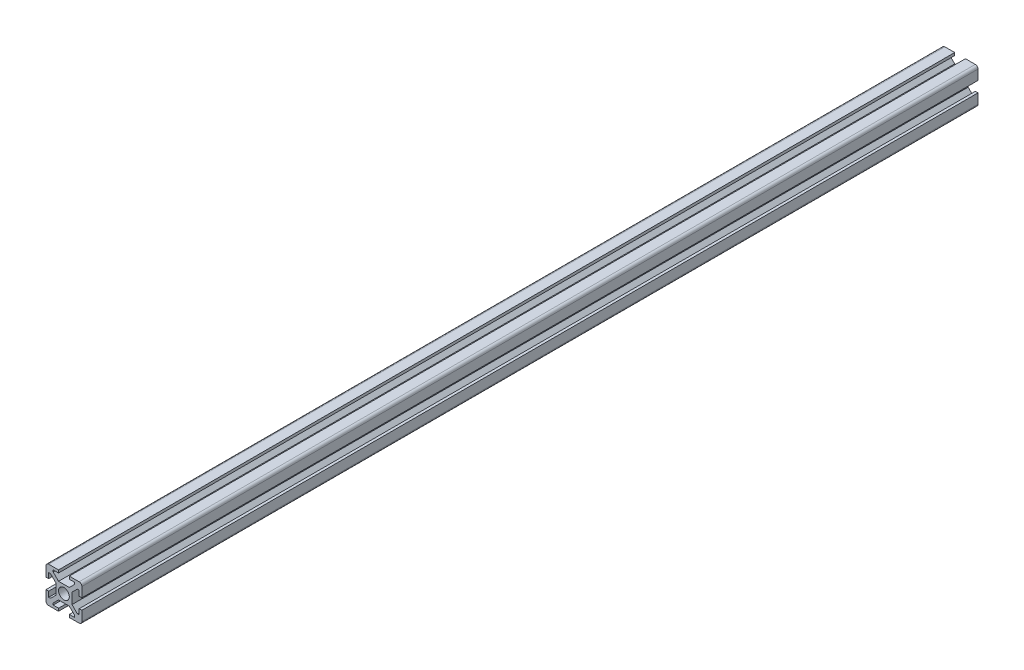
SolidWorks part; units mm, degrees
ref_plane "Plan de face" through (0, 0, 0) normal (0, 0, 1) x (1, 0, 0)
ref_plane "Plan de dessus" through (0, 0, 0) normal (0, 1, 0) x (1, 0, 0)
ref_plane "Plan de droite" through (0, 0, 0) normal (1, 0, 0) x (0, 0, -1)
sketch "Esquisse1" plane through (0, 0, 0) normal (0, 0, 1) x (1, 0, 0)
  line L0 (-10, 10) -> (10, -10) construction
  line L1 (-10, 10) -> (10, 10)
  line L2 (-10, 10) -> (-10, -10)
  line L3 (-10, -10) -> (10, -10)
  line L4 (10, 10) -> (10, -10)
  dimension "D1" = 20
extrude "Extrusion1" add sketch "Esquisse1" along normal mid plane 500
fillet "Congé1" radius 1.5 4 edges at (-10, -10, 0) (10, -10, 0) (-10, 10, 0) (10, 10, 0)
sketch "Esquisse2" plane through (0, 0, -250) normal (0, 0, -1) x (-1, 0, 0)
  line L0 (-10, 3) -> (-10, -3)
  line L1 (-10, -8.5) -> (-10, 8.5) construction
  line L2 (-10, -3) -> (-8.5, -3)
  line L3 (-8.5, -3) -> (-8.5, -6)
  line L4 (-8.5, 6) -> (-7.5, 6)
  line L5 (-4.5, -3) -> (-4.5, 3)
  line L6 (-7.5, 6) -> (-4.5, 3)
  line L7 (-8.5, 6) -> (-8.5, 3)
  line L8 (-8.5, 3) -> (-10, 3)
  line L9 (0, 0) -> (-10, 0) construction
  line L10 (-8.5, -6) -> (-7.5, -6)
  line L11 (-7.5, -6) -> (-4.5, -3)
  point P4 (-10, 0)
  dimension "D1" = 6
  dimension "D2" = 12
  dimension "D3" = 1.5
  dimension "D4" = 5.5
  dimension "D5" = 135
extrude "Enlèv. mat.-Extru.1" cut sketch "Esquisse2" against normal through all
ref_axis "Axe1" through (0, 0, 9.3338) along (0, 0, -1)
pattern_circular "Répétition circulaire1" count 4 over 360 about axis through (0, 0, 9.3338) along (0, 0, -1) of "Enlèv. mat.-Extru.1"
hole_wizard "Trou taraudé M6x1.01" positions "Esquisse4" profile "Esquisse5" tap size "M6x1.0" standard "Ansi Métrique"
sketch "Esquisse4" plane through (0, 0, -250) normal (0, 0, -1) x (-1, 0, 0)
  point P0 (0, 0)
sketch "Esquisse5" plane through (0, 0, -250) normal (1, 0, 0) x (0, 1, 0)
  line L0 (0, 0) -> (0, 31.5022)
  line L1 (0, 31.5022) -> (2.5, 30)
  line L2 (2.5, 30) -> (2.5, 24)
  line L3 (2.5, 24) -> (3, 24)
  line L4 (3, 24) -> (3, 0)
  line L5 (3, 0) -> (0, 0)
  line L10 (0, 31.5022) -> (-2.5, 30) construction
  line L11 (0, -6.35) -> (0, 107.95) construction
  dimension "Diamètre du trou pour taraudage" = 5
  dimension "Profondeur du trou pour taraudage" = 30
  dimension "Diamètre principal du filetage" = 6
  dimension "Profondeur du filetage" = 24
  dimension "Angle de pointe" = 118
mirror "Symétrie1" about plane through (0, 0, 0) normal (0, 0, 1) of "Trou taraudé M6x1.01"
